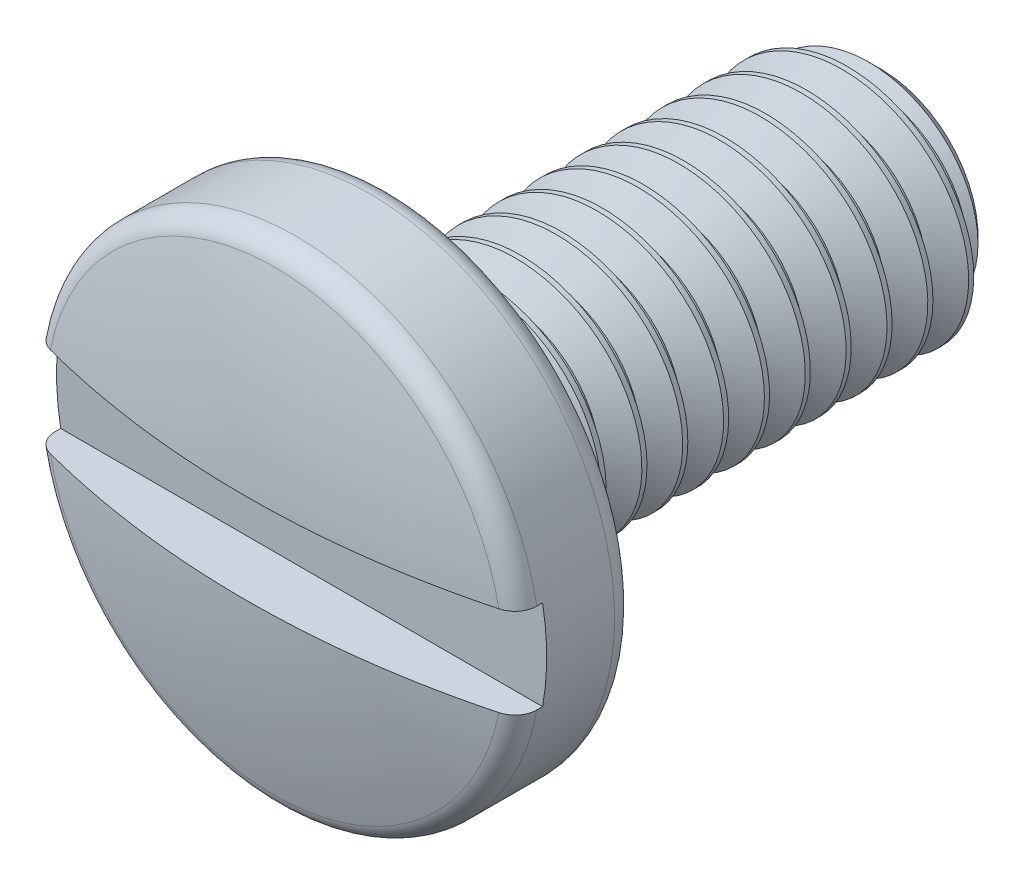
SolidWorks part; units mm, degrees
note: '?' marks a value the reader was unsure of.
material "Chrome Stainless Steel"
ref_plane "Front Plane" through (0, 0, 0) normal (0, 0, 1) x (1, 0, 0)
ref_plane "Top Plane" through (0, 0, 0) normal (0, 1, 0) x (1, 0, 0)
ref_plane "Right Plane" through (0, 0, 0) normal (1, 0, 0) x (0, 0, -1)
ref_axis "Axis1" through (0, 0, -4.5244) along (0, 0, 1)?
sketch "Sketch1" plane through (0, 0, 0) normal (0, 0, 1) x (1, 0, 0)
  line L0 (3, 0) -> (-3, 0) construction
  line L1 (0, -3) -> (0, 3) construction
  circle A0 centre (0, 0) radius 3 construction
  point P6 (0, 0)
  point P9 (0, 0)
  point P10 (-3, 0)
  point P11 (0, 3)
  point P12 (0, -3)
  point P13 (3, 0)
  dimension "Head Diameter" = 6
sketch "Sketch2" plane through (0, 0, 0) normal (1, 0, 0) x (0, 0, -1)
  line L0 (3.9, 0) -> (-3.9, 0) construction
  line L1 (3.9, -1.5) -> (3.9, 1.5) construction
  line L2 (3.9, 1.5) -> (-2.1, 1.5) construction
  line L3 (-2.1, 1.5) -> (-2.1, 2.73) construction
  line L5 (3.9, -1.5) -> (-2.1, -1.5) construction
  line L6 (-2.1, -1.5) -> (-2.1, -2.73) construction
  line L7 (2.65, 1.5) -> (2.65, -1.5) construction
  line L9 (-3.9, -3) -> (-3.9, 3) construction
  line L10 (-2.1, 1.5) -> (-2.1, 3) construction
  line L11 (-2.1, 3) -> (-3.9, 3) construction
  line L12 (-3.9, -3) -> (-2.1, -3) construction
  line L13 (-2.1, -3) -> (-2.1, -1.5) construction
  line L14 (-3, 3) -> (-3, -3) construction
  line L15 (3.8688, 1.5541) -> (4.3688, 1.5541) construction
  line L16 (4.3688, 1.5541) -> (4.1188, 1.1211) construction
  line L17 (4.1188, 1.1211) -> (3.8688, 1.5541) construction
  line L18 (3.8844, 1.5271) -> (4.3531, 1.5271) construction
  line L19 (3.9, 1.5) -> (4.3375, 1.5) construction
  line L20 (4.0875, 1.1752) -> (4.15, 1.1752) construction
  line L21 (4.1188, 1.1752) -> (4.1188, 1.1211) construction
  line L22 (4.1188, 1.5) -> (4.1187, 1.5541) construction
  line L23 (3.9, 1.5541) -> (3.9, 1.1791) construction
  line L24 (3.9, 1.1791) -> (3.525, 1.5541) construction
  line L25 (3.525, 1.5541) -> (3.9, 1.5541) construction
  line L27 (-3.9, -0.55) -> (-3.2, -0.55) construction
  line L28 (-3.9, -0.55) -> (-3.9, 0.55) construction
  line L29 (-3.9, 0.55) -> (-3.2, 0.55) construction
  line L30 (-3.2, -0.55) -> (-3.2, 0.55) construction
  arc A0 (-2.1, 2.73) -> (-2.37, 3) centre (-2.37, 2.73) ccw construction
  arc A1 (-3.27, 3) -> (-3.5308, 2.8) centre (-3.27, 2.73) ccw construction
  arc A2 (-3.5308, 2.8) -> (-3.9, 0) centre (6.9012, 0) ccw construction
  arc A3 (-2.1, -2.73) -> (-2.37, -3) centre (-2.37, -2.73) cw construction
  arc A4 (-3.27, -3) -> (-3.5308, -2.8) centre (-3.27, -2.73) cw construction
  arc A5 (-3.5308, -2.8) -> (-3.9, 0) centre (6.9012, 0) cw construction
  point P0 (3.9, 1.5)
  point P4 (0, 0)
  point P8 (3.9, 0)
  point P10 (3.9, -1.5)
  point P17 (2.65, -1.5)
  point P23 (2.65, 0)
  point P24 (2.65, 1.5)
  point P31 (-2.1, 2.73)
  point P32 (-2.37, 3)
  point P34 (-3.27, 3)
  point P35 (-3.5308, 2.8)
  point P36 (-2.1, 1.5)
  point P37 (-3.9, 0)
  point P38 (-3.5308, -2.8)
  point P39 (-3.27, -3)
  point P40 (-2.37, -3)
  point P41 (-2.1, -2.73)
  point P42 (-2.1, -1.5)
  point P45 (-3.9, 3)
  point P46 (-2.1, 3)
  point P48 (-2.1, -3)
  point P56 (-3.9, 0)
  point P61 (4.1188, 1.5)
  point P64 (4.1188, 1.5271)
  point P65 (4.15, 1.1752)
  point P66 (4.0875, 1.1752)
  point P67 (3.9, 1.5541)
  point P68 (3.8688, 1.5541)
  point P69 (3.9, 1.5)
  point P70 (4.3375, 1.5)
  point P71 (4.3688, 1.5541)
  point P76 (3.9, 1.1791)
  point P80 (-3.9, 0)
  point P82 (-3.9, 0.55)
  point P83 (-3.9, -0.55)
  point P84 (-3.2, 0.55)
  point P85 (-3.2, -0.55)
  dimension "Head Height" = 1.8
  dimension "Length" = 6
  dimension "D3" = 0.0625
  dimension "D1" = 45
ref_plane "Plane1" through (0, 0, -3.9) normal (0, 0, 1) x (1, 0, 0)
ref_plane "Plane2" through (0, 0, 2.1) normal (0, 0, 1) x (1, 0, 0)
sketch "Sketch3" plane through (0, 0, 0) normal (1, 0, 0) x (0, 0, -1)
  line L0 (3.9, 0) -> (-3.9, 0) construction
  line L1 (3.9, 0) -> (-3.9, 0)
  line L2 (3.9, -1.5) -> (3.9, 1.5) construction
  line L3 (3.9, 1.5) -> (-2.1, 1.5) construction
  line L4 (-2.1, 1.5) -> (-2.1, 2.73) construction
  line L5 (-2.1, 3) -> (-3.9, 3) construction
  line L6 (3.9, 0) -> (3.9, 1.1791)
  line L7 (3.5791, 1.5) -> (-2.1, 1.5)
  line L8 (-2.1, 1.5) -> (-2.1, 2.73)
  line L9 (-2.37, 3) -> (-3.27, 3)
  line L10 (3.9, 1.1791) -> (3.525, 1.5541) construction
  line L11 (3.9, 1.1791) -> (3.5791, 1.5)
  arc A0 (-2.1, 2.73) -> (-2.37, 3) centre (-2.37, 2.73) ccw construction
  arc A1 (-3.27, 3) -> (-3.5308, 2.8) centre (-3.27, 2.73) ccw construction
  arc A2 (-3.5308, 2.8) -> (-3.9, 0) centre (6.9012, 0) ccw construction
  arc A3 (-2.1, 2.73) -> (-2.37, 3) centre (-2.37, 2.73) ccw
  arc A4 (-3.27, 3) -> (-3.5308, 2.8) centre (-3.27, 2.73) ccw
  arc A5 (-3.5308, 2.8) -> (-3.9, 0) centre (6.9012, 0) ccw
revolve "Revolve1" add sketch "Sketch3" angle 360 about L1
sketch "Sketch4" plane through (0, 0, 0) normal (1, 0, 0) x (0, 0, -1)
  line L0 (-3.9, -3) -> (-3.9, 3) construction
  line L1 (-3.9, -0.55) -> (-3.2, -0.55) construction
  line L2 (-3.2, -0.55) -> (-3.2, 0.55) construction
  line L3 (-3.9, 0.55) -> (-3.2, 0.55) construction
  line L4 (-3.9, -0.55) -> (-3.9, 0.55)
  line L5 (-3.9, -0.55) -> (-3.2, -0.55)
  line L6 (-3.2, -0.55) -> (-3.2, 0.55)
  line L7 (-3.9, 0.55) -> (-3.2, 0.55)
extrude "Cut-Extrude1" cut sketch "Sketch4" against normal through all both and the other way through all
sketch "Sketch5" plane through (0, 0, -3.9) normal (0, 0, 1) x (1, 0, 0)
  circle A0 centre (0, 0) radius 1.5
curve "Helix/Spiral1" pitch 0.5 height 6.5 turns 13
sketch "Sketch6" plane through (0, 0, 0) normal (1, 0, 0) x (0, 0, -1)
  line L0 (4.0875, 1.1752) -> (4.15, 1.1752) construction
  line L1 (3.8844, 1.5271) -> (4.3531, 1.5271) construction
  line L2 (4.0875, 1.1752) -> (4.15, 1.1752)
  line L3 (3.8844, 1.5271) -> (4.3531, 1.5271)
  line L4 (4.3688, 1.5541) -> (4.1188, 1.1211) construction
  line L5 (4.1188, 1.1211) -> (3.8688, 1.5541) construction
  line L6 (4.3531, 1.5271) -> (4.15, 1.1752)
  line L7 (4.0875, 1.1752) -> (3.8844, 1.5271)
sweep "Cut-Sweep1" cut profiles "Sketch6" path "Helix/Spiral1" align with end faces yes
sketch "Sketch7" plane through (0, 0, 2.1) normal (0, 0, 1) x (1, 0, 0)
  circle A0 centre (0, 0) radius 1.5541
  point P3 (0, 1.5541)
extrude "Boss-Extrude1" add sketch "Sketch7" along normal up to vertex (1.1 mm away) and the other way through all draft 45 up to point (0, 0.55, 3.2)
equation "\"Rad1@Sketch2\" = \"Head Height@Sketch2\" * .15"
equation "\"D3@Sketch2\" = \"Thread Pitch@Sketch2\" / 8"
equation "\"Thread Note@Sketch2\" = \"Thread Pitch@Sketch2\" * 2.5"
equation "\"Chamfer@Sketch2\" = \"Thread Pitch@Sketch2\" * .75"
equation "\"D3@Helix/Spiral1\" = \"Length@Sketch2\" + \"Thread Pitch@Sketch2\""
equation "\"D4@Helix/Spiral1\" = \"Thread Pitch@Sketch2\""
